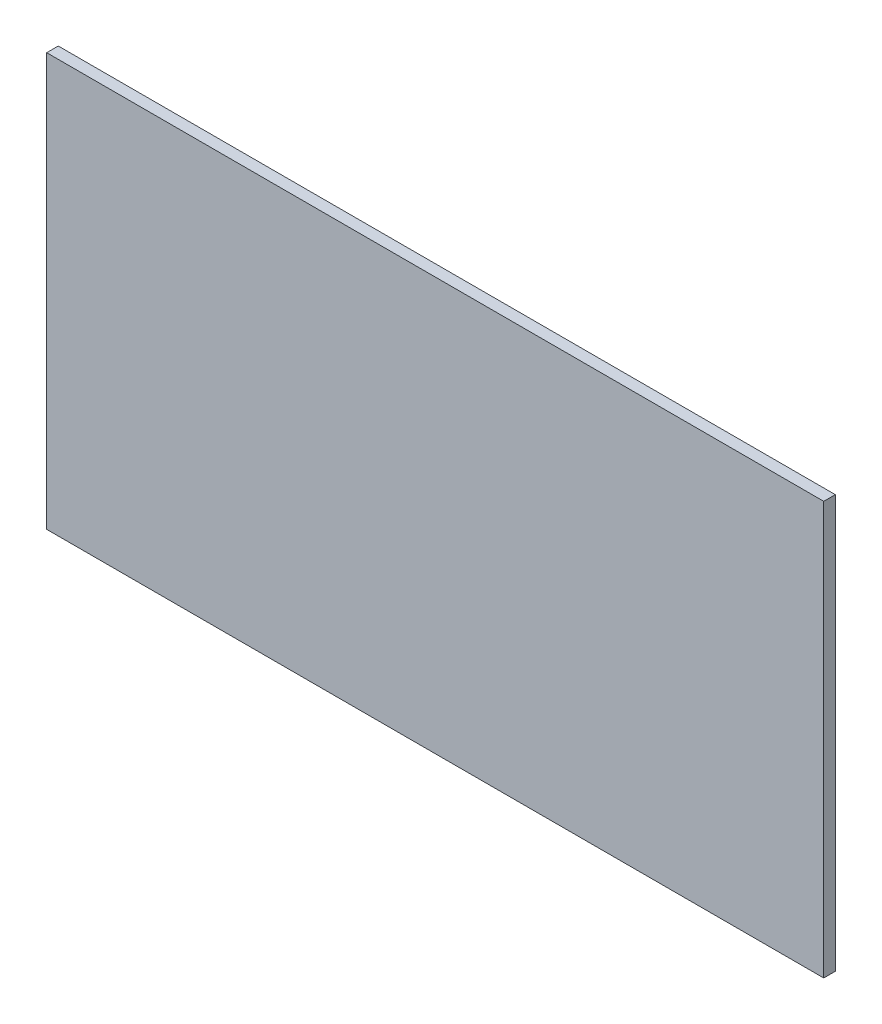
SolidWorks part; units mm, degrees
ref_plane "Ön Düzlem" through (0, 0, 0) normal (0, 0, 1) x (1, 0, 0)
ref_plane "Üst Düzlem" through (0, 0, 0) normal (0, 1, 0) x (1, 0, 0)
ref_plane "Sağ Düzlem" through (0, 0, 0) normal (1, 0, 0) x (0, 0, -1)
sketch "Çizim1" plane through (0, 0, 0) normal (0, 0, 1) x (1, 0, 0)
  line L1 (0, 0) -> (1508, 0)
  line L2 (0, 0) -> (0, -1970)
  line L3 (0, -1970) -> (1508, -1970)
  line L4 (1508, 0) -> (1508, -1970)
  dimension "D1" = 1508
  dimension "D2" = 1970
base flange "Taban-Flanş1" sketch "Çizim1" thickness 15 reverse thickness direction no parameters "D1"=10
sketch "Çizim2" plane through (0, 0, 0) normal (0, 0, 1) x (1, 0, 0)
  line L0 (1508, -1970) -> (1508, 0) construction
  line L1 (0, 0) -> (501, 0)
  line L2 (0, 0) -> (0, -1970)
  line L3 (0, -1970) -> (501, -1970)
  line L4 (501, 0) -> (501, -1970)
  line L5 (0, -1970) -> (1508, -1970) construction
  dimension "D1" = 1007
  dimension "D2" = 1970
extrude "Kes-Ekstrüzyon1" cut sketch "Çizim2" against normal through all both and the other way through all
sketch "Çizim3" plane through (0, 0, 0) normal (0, 0, 1) x (1, 0, 0)
  line L0 (1508, -1970) -> (1508, 0) construction
  line L1 (501, 0) -> (1508, 0)
  line L2 (501, 0) -> (501, -310)
  line L3 (501, -310) -> (1508, -310)
  line L4 (1508, 0) -> (1508, -310)
  line L5 (501, -1970) -> (1508, -1970) construction
  dimension "D1" = 1660
  dimension "D2" = 1007
  dimension "D3" = 310
extrude "Kes-Ekstrüzyon2" cut sketch "Çizim3" against normal through all both and the other way through all
sketch "Çizim4" plane through (0, 0, 0) normal (0, 0, 1) x (1, 0, 0)
  line L0 (1508, -1970) -> (1508, -310) construction
  line L1 (501, -310) -> (1508, -310)
  line L2 (501, -310) -> (501, -1435)
  line L3 (501, -1435) -> (1508, -1435)
  line L4 (1508, -310) -> (1508, -1435)
  line L5 (501, -1970) -> (1508, -1970) construction
  dimension "D1" = 535
extrude "Kes-Ekstrüzyon3" cut sketch "Çizim4" against normal through all both and the other way through all
sketch "Büküm-Çizgileri1" [suppressed] plane through (0, 0, 0) normal (0, 1, 0) x (1, 0, 0)
sketch "Sınırlandırma-Kutusu1" [suppressed] plane through (0, 0, 0) normal (0, 1, 0) x (1, 0, 0)
sheet metal parameters "Sac-Levha1" thickness 15 parameters "D1"=10
flat pattern "Düz-Çoğaltma1" [suppressed]
sketch "Büküm-Çizgileri2" plane through (0, 0, 0) normal (0, 1, 0) x (1, 0, 0)
sketch3d "Sınırlandırma-Kutusu2" [suppressed]
  line L0 (-1508, 0, 0) -> (-1508, -1970, 0) construction
  line L1 (0, 0, 0) -> (0, -1970, 0) construction
  line L2 (-1508, 0, 0) -> (0, 0, 0) construction
  line L3 (-1508, -1970, 0) -> (0, -1970, 0) construction
sheet metal parameters "Sac-Levha2" thickness 15 parameters "D1"=10
flat pattern "Düz-Çoğaltma1"
sketch "Büküm-Çizgileri2" plane through (0, 0, 0) normal (0, 1, 0) x (1, 0, 0)
sketch3d "Sınırlandırma-Kutusu2" [suppressed]
  line L0 (1508, 0, 0) -> (1508, -1970, 0) construction
  line L1 (501, 0, 0) -> (501, -1970, 0) construction
  line L2 (1508, 0, 0) -> (501, 0, 0) construction
  line L3 (1508, -1970, 0) -> (501, -1970, 0) construction
sheet metal parameters "Sac-Levha3" thickness 15 parameters "D1"=10
flat pattern "Düz-Çoğaltma1"
sketch "Büküm-Çizgileri2" plane through (0, 0, 0) normal (0, 1, 0) x (1, 0, 0)
sketch3d "Sınırlandırma-Kutusu2" [suppressed]
  line L0 (1508, -310, 0) -> (1508, -1970, 0) construction
  line L1 (501, -310, 0) -> (501, -1970, 0) construction
  line L2 (1508, -310, 0) -> (501, -310, 0) construction
  line L3 (1508, -1970, 0) -> (501, -1970, 0) construction
sheet metal parameters "Sac-Levha4" thickness 15 parameters "D1"=10
flat pattern "Düz-Çoğaltma1"
sketch "Büküm-Çizgileri2" plane through (0, 0, 0) normal (0, 1, 0) x (1, 0, 0)
sketch3d "Sınırlandırma-Kutusu2" [suppressed]
  line L0 (501, -1970, 0) -> (1508, -1970, 0) construction
  line L1 (501, -1435, 0) -> (1508, -1435, 0) construction
  line L2 (501, -1970, 0) -> (501, -1435, 0) construction
  line L3 (1508, -1970, 0) -> (1508, -1435, 0) construction
